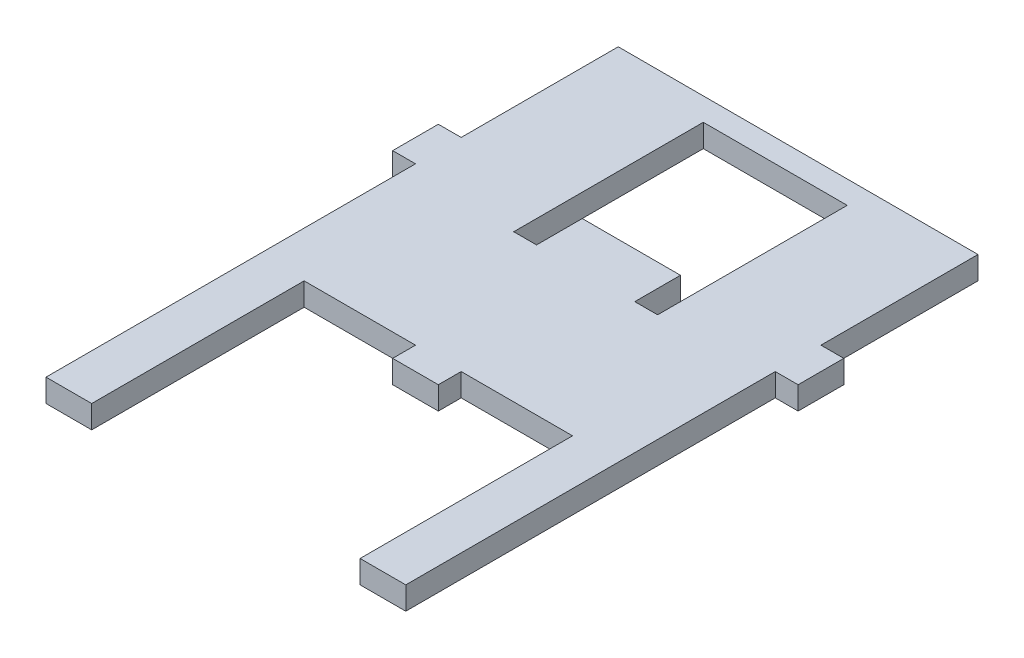
SolidWorks part; units mm, degrees
material "Acrylic (Medium-high impact)"
ref_plane "Front Plane" through (0, 0, 0) normal (0, 0, 1) x (1, 0, 0)
ref_plane "Top Plane" through (0, 0, 0) normal (0, 1, 0) x (1, 0, 0)
ref_plane "Right Plane" through (0, 0, 0) normal (1, 0, 0) x (0, 0, -1)
sketch "Sketch1" plane through (0, 0, 0) normal (0, 1, 0) x (1, 0, 0)
  line L1 (-50, -50) -> (50, -50)
  line L2 (-50, -50) -> (-50, 50)
  line L3 (-50, 50) -> (50, 50)
  line L4 (50, -50) -> (50, 50)
  line L5 (-50, -50) -> (50, 50) construction
  line L6 (-50, 50) -> (50, -50) construction
  point P0 (0, 0)
  dimension "D1" = 100
  dimension "D2" = 100
extrude "Boss-Extrude1" add sketch "Sketch1" along normal blind 6.35
ref_point "Point1"
ref_axis "Axis1" through (0, 6.35, 0) along (0, 1, 0)
sketch "Sketch2" plane through (-50, 0, 0) normal (-1, 0, 0) x (0, 0, 1)
  line L0 (-6.35, 0) -> (-6.35, 6.35)
  line L1 (-6.35, 0) -> (6.35, 0)
  line L2 (-6.35, 6.35) -> (6.35, 6.35)
  line L3 (6.35, 0) -> (6.35, 6.35)
  line L4 (-6.35, 0) -> (6.35, 6.35) construction
  line L5 (-6.35, 6.35) -> (6.35, 0) construction
  line L6 (-50, 6.35) -> (50, 6.35) construction
  line L7 (50, 6.35) -> (50, 0) construction
  point P1 (0, 3.175)
  dimension "D1" = 3.175
  dimension "D2" = 6.35
  dimension "D3" = 12.7
  dimension "D4" = 50
extrude "Boss-Extrude2" add sketch "Sketch2" along normal blind 6.35 contours L3 L2 L0 L1
pattern_circular "CirPattern1" count 3 every 90 about axis through (0, 6.35, 0) along (0, 1, 0) of "Boss-Extrude2"
sketch "Sketch3" plane through (0, 6.35, 0) normal (0, 1, 0) x (1, 0, 0)
  line L1 (-50, -50) -> (50, -50)
  line L2 (-50, -50) -> (-50, 50)
  line L3 (-50, 50) -> (50, 50)
  line L4 (50, -50) -> (50, 50)
  line L5 (-50, -50) -> (50, 50) construction
  line L6 (-50, 50) -> (50, -50) construction
  point P0 (0, 0)
  dimension "D1" = 100
  dimension "D2" = 100
sketch "Sketch4" plane through (0, 0, 50) normal (0, 0, 1) x (1, 0, 0)
  line L0 (-50, 0) -> (-6.35, 0) construction
  line L1 (-50, 6.35) -> (-37.3, 6.35)
  line L2 (-50, 6.35) -> (-50, 0)
  line L3 (-50, 0) -> (-37.3, 0)
  line L4 (-37.3, 6.35) -> (-37.3, 0)
  dimension "D1" = 12.7
extrude "Boss-Extrude3" add sketch "Sketch4" along normal blind 59.05
ref_plane "Plane1" through (0, 0, 0) normal (1, 0, 0) x (0, 0, -1)
mirror "Mirror1" about plane through (0, 0, 0) normal (1, 0, 0) of "Boss-Extrude3"
sketch "Sketch5" plane through (0, 6.35, 0) normal (0, 1, 0) x (1, 0, 0)
  line L0 (-20, 3.65) -> (-20, 43.65)
  line L1 (-20, 3.65) -> (20, 3.65)
  line L2 (-20, 43.65) -> (20, 43.65)
  line L3 (20, 3.65) -> (20, 43.65)
  line L4 (-20, 3.65) -> (20, 43.65) construction
  line L5 (-20, 43.65) -> (20, 3.65) construction
  line L6 (50, 6.35) -> (50, 50) construction
  line L7 (50, 50) -> (-50, 50) construction
  point P1 (0, 23.65)
  dimension "D1" = 40
  dimension "D2" = 40
  dimension "D3" = 50
  dimension "D4" = 6.35
extrude "Cut-Extrude1" cut sketch "Sketch5" against normal through all
sketch "Sketch6" plane through (0, 6.35, 0) normal (0, 1, 0) x (1, 0, 0)
  line L1 (-20, 3.65) -> (-13.65, 3.65)
  line L2 (-20, 3.65) -> (-20, -9.05)
  line L3 (-20, -9.05) -> (-13.65, -9.05)
  line L4 (-13.65, 3.65) -> (-13.65, -9.05)
  dimension "D1" = 6.35
  dimension "D2" = 12.7
extrude "Cut-Extrude2" cut sketch "Sketch6" against normal through all
mirror "Mirror2" about plane through (0, 0, 0) normal (1, 0, 0) of "Cut-Extrude2"
